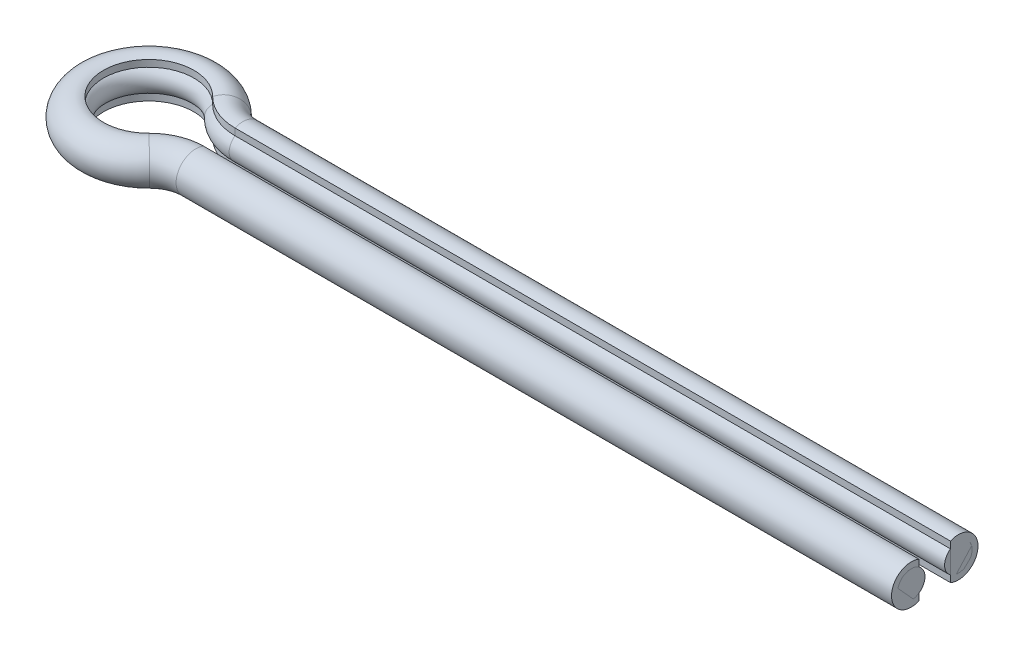
SolidWorks part; units mm, degrees
ref_plane "Front Plane" through (0, 0, 0) normal (0, 0, 1) x (1, 0, 0)
ref_plane "Top Plane" through (0, 0, 0) normal (0, 1, 0) x (1, 0, 0)
ref_plane "Right Plane" through (0, 0, 0) normal (1, 0, 0) x (0, 0, -1)
sketch "Sketch1" plane through (0, 0, 0) normal (0, 1, 0) x (1, 0, 0)
  line L1 (-41.0209, -3) -> (50, -3)
  line L2 (-41.0209, 3) -> (50, 3)
  arc A0 (-45.1993, 4.745) -> (-45.1993, -4.745) centre (-50, 0) ccw
  arc A2 (-41.0209, -3) -> (-45.1993, -4.745) centre (-41.0209, -8.875) ccw
  arc A3 (-41.0209, 3) -> (-45.1993, 4.745) centre (-41.0209, 8.875) cw
  point P3 (-50, -3)
  point P5 (-50, 3)
  dimension "D4" = 13.5
  dimension "D6" = 11.75
  dimension "D3" = 45.1993
  dimension "D1" = 50
  dimension "D2" = 41.0209
ref_plane "Plane2" through (50, 0, -3) normal (1, 0, 0) x (0, 0, -1)
sketch "Sketch5" plane through (50, 0, -3) normal (1, 0, 0) x (0, 0, -1)
  line L0 (1.745, 0) -> (0, 0) construction
  line L2 (3.75, 0) -> (-9.75, 0) construction
  circle A2 centre (0, 0) radius 1.75
  dimension "D1" = 3.5
  dimension "D2" = 3
sweep "Sweep1" add profiles "Sketch5" path "Sketch1"
sketch "Sketch9" plane through (50, 0, -3) normal (1, 0, 0) x (0, 0, -1)
  line L0 (1.745, 0) -> (0, 0) construction
  line L1 (3.75, 0) -> (-9.75, 0) construction
  line L3 (-1, 2.2913) -> (-1, -2.2913)
  arc A0 (-1, -2.2913) -> (-1, 2.2913) centre (0, 0) ccw
  dimension "D1" = 5
  dimension "D2" = 2
  dimension "D3" = 3
sketch "Sketch1<2>" plane through (0, 0, 0) normal (0, 1, 0) x (1, 0, 0) same geometry as "Sketch1"
sweep "Sweep3" add profiles "Sketch9" path "Sketch1<3>"
sketch "Sketch1<3>" plane through (0, 0, 0) normal (0, 1, 0) x (1, 0, 0) same geometry as "Sketch1"
